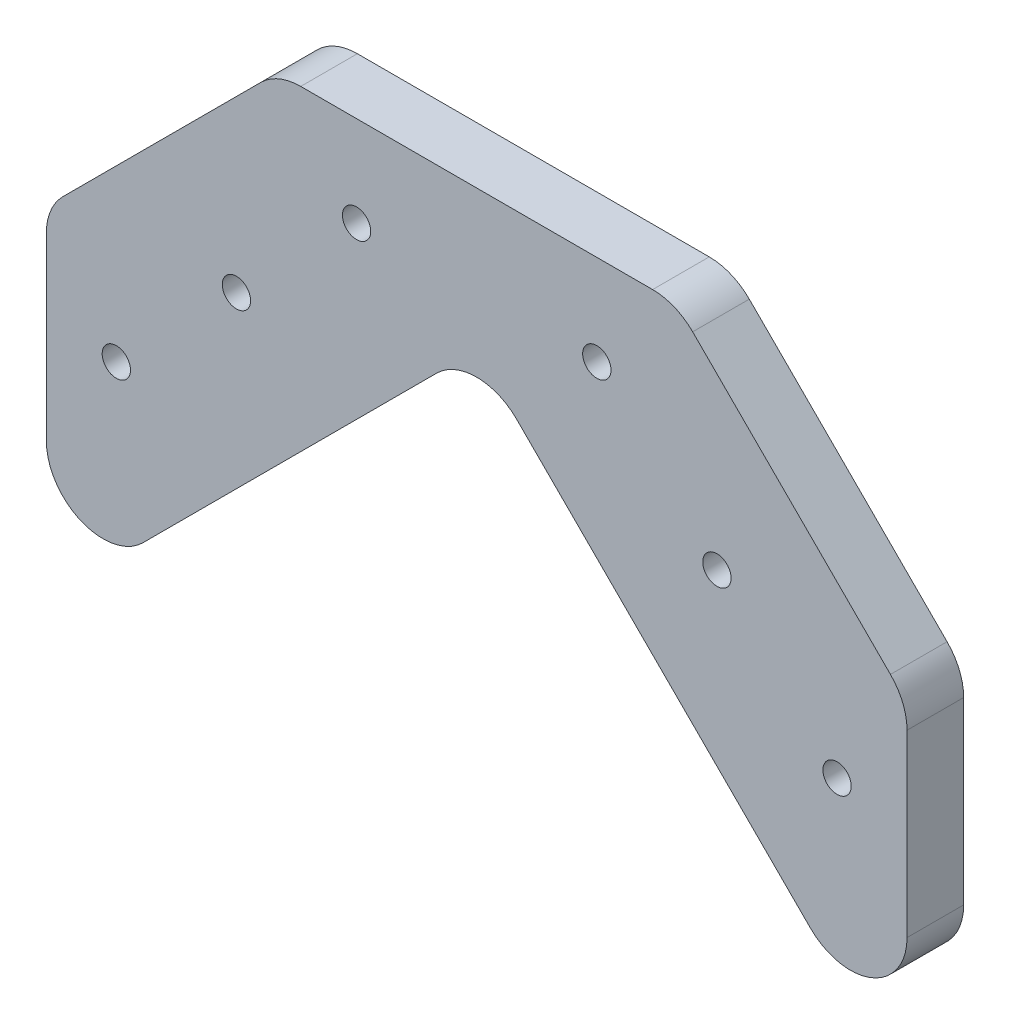
SolidWorks part; units mm, degrees
ref_plane "Front Plane" through (0, 0, 0) normal (0, 0, 1) x (1, 0, 0)
ref_plane "Top Plane" through (0, 0, 0) normal (0, 1, 0) x (1, 0, 0)
ref_plane "Right Plane" through (0, 0, 0) normal (1, 0, 0) x (0, 0, -1)
sketch "Sketch1" plane through (0, 0, 0) normal (0, 0, 1) x (1, 0, 0)
  line L0 (0, 110) -> (0, 0) construction
  line L1 (-40, 0) -> (-40, 70) construction
  line L2 (-40, 70) -> (0, 110) construction
  line L3 (0, 0) -> (-40, 0) construction
  line L4 (-38, 74.8284) -> (0, 112.8284)
  line L5 (-38, 74.8284) -> (-38, 104.8284)
  line L6 (-38, 104.8284) -> (-17.6066, 125.2218)
  line L7 (-38, 89.8284) -> (0, 127.8284) construction
  line L8 (0, 112.8284) -> (0, 142.8284) construction
  line L9 (38, 104.8284) -> (17.6066, 125.2218)
  line L10 (38, 74.8284) -> (0, 112.8284)
  line L11 (38, 74.8284) -> (38, 104.8284)
  line L12 (0, 125.2218) -> (-17.6066, 125.2218)
  line L13 (0, 125.2218) -> (17.6066, 125.2218)
  circle A0 centre (-31.8198, 96.0086) radius 1.25
  circle A1 centre (-21.2132, 106.6152) radius 1.25
  circle A2 centre (-10.6066, 117.2218) radius 1.25
  circle A4 centre (10.6066, 117.2218) radius 1.25
  circle A5 centre (21.2132, 106.6152) radius 1.25
  circle A6 centre (31.8198, 96.0086) radius 1.25
  point P21 (0, 127.8284)
  dimension "D7" = 2.5
  dimension "D1" = 70
  dimension "D2" = 40
  dimension "D3" = 40
  dimension "D4" = 4
  dimension "D5" = 2
  dimension "D6" = 30
  dimension "D8" = 15
  dimension "D9" = 15
  dimension "D10" = 15
  dimension "D11" = 8
extrude "Boss-Extrude1" add sketch "Sketch1" along normal blind 5
fillet "Fillet1" radius 5 7 edges at (0, 112.8284, 2.5) (-38, 74.8284, 2.5) (38, 74.8284, 2.5) (38, 104.8284, 2.5) (-38, 104.8284, 2.5) (17.6066, 125.2218, 2.5) (-17.6066, 125.2218, 2.5)
